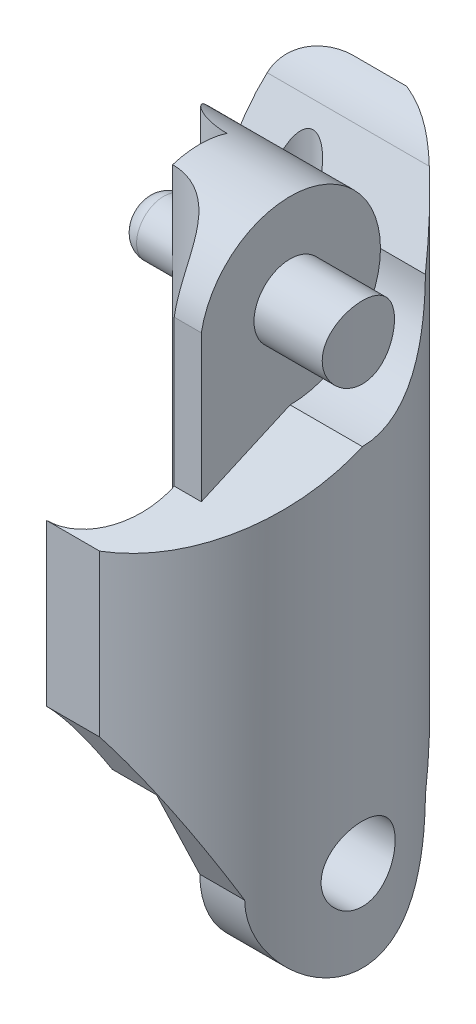
SolidWorks part; units mm, degrees
ref_plane "Front Plane" through (0, 0, 0) normal (0, 0, 1) x (1, 0, 0)
ref_plane "Top Plane" through (0, 0, 0) normal (0, 1, 0) x (1, 0, 0)
ref_plane "Right Plane" through (0, 0, 0) normal (1, 0, 0) x (0, 0, -1)
sketch "Sketch1" plane through (0, 0, 0) normal (0, 1, 0) x (1, 0, 0)
  line L0 (-2.958, 8.5) -> (2.958, 8.5)
  line L1 (-2.958, -8.5) -> (2.958, -8.5)
  arc A0 (-2.958, 8.5) -> (-2.958, -8.5) centre (0, 0) ccw
  arc A1 (2.958, 8.5) -> (2.958, -8.5) centre (0, 0) cw
  point P9 (-9, 0)
  point P10 (9, 0)
  dimension "D1" = 18
  dimension "D2" = 17
extrude "Boss-Extrude1" add sketch "Sketch1" along normal blind 35
sketch "Sketch2" plane through (0, 0, 0) normal (0, -1, 0) x (1, 0, 0)
  circle A0 centre (0, -5) radius 1.27
  circle A1 centre (0, 5) radius 1.27
  dimension "D1" = 2.54
  dimension "D2" = 5
  dimension "D3" = 5
extrude "Cut-Extrude1" cut sketch "Sketch2" against normal blind 35
sketch "Sketch3" plane through (0, 0, -8.5) normal (0, 0, -1) x (-1, 0, 0)
  line L0 (5, 0) -> (5, 10)
  line L1 (5, 10) -> (-5, 10)
  line L2 (-5, 10) -> (-5, 0)
  line L3 (5, 0) -> (-5, 0)
  line L4 (-2.958, 0) -> (2.958, 0) construction
  point P10 (0, 0)
  dimension "D1" = 10
  dimension "D2" = 10
extrude "Cut-Extrude2" cut sketch "Sketch3" against normal up to surface (17 mm away) up to face at (0, 17.5, 8.5)
sketch "Sketch4" plane through (5, 0, 0) normal (-1, 0, 0) x (0, 0, 1)
  line L0 (-7.4833, 10) -> (-5, 5)
  line L1 (8.5, 12.3086) -> (5, 5)
  line L2 (7.4833, 0) -> (-7.4833, 0) construction
  line L3 (-7.4833, 10) -> (-9.8579, -1.8222)
  line L4 (-9.8579, -1.8222) -> (9.8579, -1.8222)
  line L6 (8.5, 35) -> (8.5, 10) construction
  line L7 (9.8579, -1.8222) -> (8.5, 12.3086)
  arc A0 (-5, 5) -> (5, 5) centre (0, 5) ccw
  circle A1 centre (0, 5) radius 2.05
  point P7 (0, 0)
  dimension "D1" = 4.1
  dimension "D2" = 5
  dimension "D3" = 12.0584
  dimension "D4" = 37.769
extrude "Cut-Extrude3" cut sketch "Sketch4" against normal mid plane 35
ref_plane "Plane1" through (-2.958, 0, 0) normal (-1, 0, 0) x (0, 0, 1)
sketch "Sketch6" plane through (-2.958, 0, 0) normal (-1, 0, 0) x (0, 0, 1)
  line L0 (8.5, 21.2199) -> (0, 25)
  line L1 (8.5, 35) -> (8.5, 12.3086) construction
  line L2 (-5, 30) -> (-6.7559, 33.5353)
  line L3 (8.5, 35) -> (-8.5, 35) construction
  line L4 (8.5, 21.2199) -> (17.803, 42.886)
  line L6 (-7.4833, 10) -> (-5, 5) construction
  line L7 (-8.5, 35) -> (17.803, 42.886)
  arc A0 (0, 25) -> (-5, 30) centre (0, 30) cw
  circle A1 centre (0, 30) radius 2
  arc A2 (-6.7559, 33.5353) -> (-8.5, 35) centre (-9.3069, 32.2683) ccw
  dimension "D1" = 5
  dimension "D3" = 4
  dimension "D2" = 5
  dimension "D4" = 8.5
extrude "Cut-Extrude5" cut sketch "Sketch6" against normal blind 9.6 from surface starting at face at (5, 7.05, 0)
sketch "Sketch7" plane through (5, 0, 0) normal (1, 0, 0) x (0, 0, -1)
  line L0 (5, 30) -> (6.7559, 33.5353)
  line L2 (-8.3419, 47.5367) -> (-13.1682, 33.5285)
  line L3 (-7.4833, 35) -> (7.4833, 35) construction
  line L4 (-4.9155, 30.9155) -> (-4.9155, 22.814)
  line L5 (-7.4833, 21.6721) -> (0, 25) construction
  line L6 (-4.9155, 22.814) -> (-10.0468, 20.532)
  line L7 (-10.0468, 20.532) -> (-13.1682, 33.5285)
  line L8 (6.7559, 33.5353) -> (5, 30) construction
  line L9 (8.5, 35) -> (-8.3419, 47.5367)
  arc A0 (5, 30) -> (-4.9155, 30.9155) centre (0, 30) ccw
  arc A1 (6.7559, 33.5353) -> (8.5, 35) centre (9.3069, 32.2683) cw
  arc A2 (7.4833, 34.4564) -> (6.7559, 33.5353) centre (9.3069, 32.2683) ccw construction
  dimension "D1" = 5
fillet "Fillet3" radius 1 2 edges at (0, 10, -3.73) (0, 10, 6.27)
extrude "Cut-Extrude6" cut sketch "Sketch6<3>" along normal blind 6.604 from surface starting at face at (-5, 2.95, 0)
sketch "Sketch6<3>" plane through (-2.958, 0, 0) normal (-1, 0, 0) x (0, 0, 1) same geometry as "Sketch6"
extrude "Cut-Extrude7" cut sketch "Sketch7" against normal blind 14.986
sketch "Sketch8" plane through (0, 10, 0) normal (0, -1, 0) x (1, 0, 0)
  line L0 (0, 1.5) -> (0, -1.5)
  line L1 (-2.958, -8.5) -> (2.958, -8.5) construction
  line L2 (2.958, 8.5) -> (-2.958, 8.5) construction
  line L3 (0, 8.5) -> (-4.7901, 15.219)
  line L4 (-4.7901, 15.219) -> (-17.8556, -9.7177)
  line L5 (-17.8556, -9.7177) -> (-4.7901, -16.0136)
  line L6 (-4.7901, -16.0136) -> (0, -8.5)
  arc A0 (0, -1.5) -> (0, -8.5) centre (0, -5) ccw
  arc A1 (0, 1.5) -> (0, 8.5) centre (0, 5) ccw
  circle A2 centre (0, 5) radius 2.27 construction
  circle A3 centre (0, -5) radius 2.27 construction
extrude "Cut-Extrude8" cut sketch "Sketch8" against normal mid plane 62.992
sketch "Sketch9" plane through (0, 0, 0) normal (-1, 0, 0) x (0, 0, 1)
  line L0 (7.3945, 10) -> (-7.4833, 10) construction
  circle A0 centre (0, 16) radius 1.5
  dimension "D2" = 3
  dimension "D1" = 6
extrude "Cut-Extrude9" cut sketch "Sketch9" against normal blind 8.382
sketch "Sketch11" plane through (0, 0, 0) normal (-1, 0, 0) x (0, 0, 1)
  circle A0 centre (0, 16) radius 2
  dimension "D1" = 4
extrude "Cut-Extrude10" cut sketch "Sketch11" against normal mid plane 6.2
sketch "Sketch12" plane through (0, 0, 0) normal (-1, 0, 0) x (0, 0, 1)
  line L0 (0, 18) -> (0, 19.5)
  line L1 (0, 14) -> (0, 12.5)
  arc A0 (1.5, 17.3229) -> (-1.5, 17.3229) centre (0, 16) ccw construction
  arc A1 (-1.5, 14.6771) -> (1.5, 14.6771) centre (0, 16) ccw construction
  arc A2 (0, 19.5) -> (0, 12.5) centre (0, 16) cw
  arc A3 (1.5, 14.6771) -> (1.5, 17.3229) centre (0, 16) ccw construction
  arc A4 (0, 18) -> (0, 14) centre (0, 16) cw
  dimension "D1" = 1.5
extrude "Boss-Extrude2" add sketch "Sketch12" against normal blind 3.862
sketch "Sketch13" plane through (0, 0, 0) normal (-1, 0, 0) x (0, 0, 1)
  line L0 (1.5, 34.7697) -> (1.5, 19.1623) construction
  circle A0 centre (0, 30) radius 1.5
  circle A1 centre (0, 30) radius 2 construction
extrude "Boss-Extrude4" add sketch "Sketch13" along normal blind 3
fillet "Fillet5" radius 1 1 edges at (-3, 30, 1.5)
